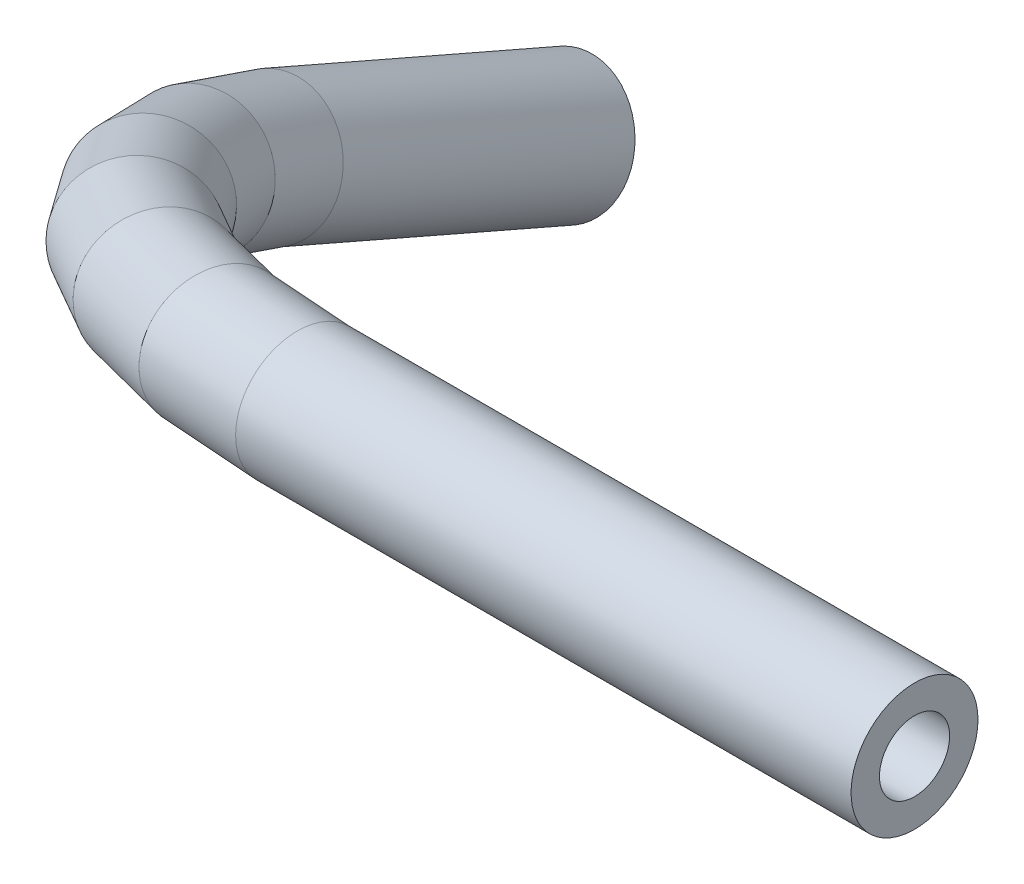
SolidWorks part; units mm, degrees
ref_plane "Front Plane" through (0, 0, 0) normal (0, 0, 1) x (1, 0, 0)
ref_plane "Top Plane" through (0, 0, 0) normal (0, 1, 0) x (1, 0, 0)
ref_plane "Right Plane" through (0, 0, 0) normal (1, 0, 0) x (0, 0, -1)
sketch3d "Path"
  line L0 (-29.2, -13, 22.5167) -> (-44.5, -13, 22.5167)
  line L1 (-44.5, -13, 22.5167) -> (-46.9588, -13.1292, 22.2198)
  line L2 (-46.9588, -13.1292, 22.2198) -> (-49.25, -13.5079, 21.3496)
  line L3 (-49.25, -13.5079, 21.3496) -> (-51.2175, -14.1104, 19.9653)
  line L4 (-51.2175, -14.1104, 19.9653) -> (-52.7272, -14.8956, 18.1613)
  line L5 (-52.7272, -14.8956, 18.1613) -> (-53.6763, -15.81, 16.0604)
  line L6 (-53.6763, -15.81, 16.0604) -> (-54, -16.7912, 13.8059)
  line L7 (-54, -16.7912, 13.8059) -> (-54, -20.0065, 6.4184)
ref_plane "Start Plane" through (-29.2, 0, 0) normal (1, 0, 0) x (0, 0, -1)
sketch "Profile" plane through (-29.2, 0, 0) normal (1, 0, 0) x (0, 0, -1)
  circle A0 centre (-22.5167, -13) radius 1.5875
  circle A1 centre (-22.5167, -13) radius 0.8775
sweep "Tube" add profiles "Profile" path "Path"
ref_axis "Engine Axis" through (-27.8806, 0, 0) along (-1, 0, 0)
